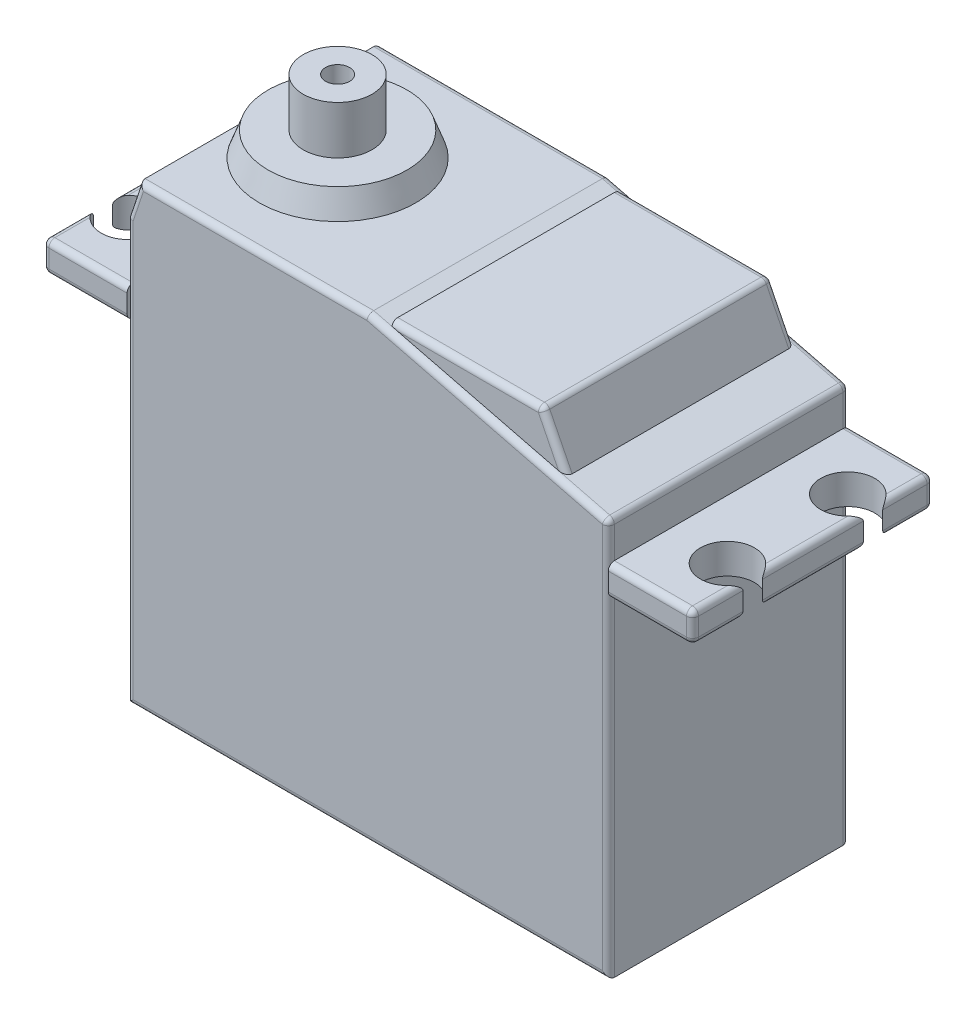
SolidWorks part; units mm, degrees
material "ABS"
ref_plane "Front Plane" through (0, 0, 0) normal (0, 0, 1) x (1, 0, 0)
ref_plane "Top Plane" through (0, 0, 0) normal (0, 1, 0) x (1, 0, 0)
ref_plane "Right Plane" through (0, 0, 0) normal (1, 0, 0) x (0, 0, -1)
sketch "Sketch2" plane through (0, 0, 0) normal (0, 1, 0) x (1, 0, 0)
  line L1 (0, 0) -> (40, 0)
  line L2 (0, 0) -> (0, 20)
  line L3 (0, 20) -> (40, 20)
  line L4 (40, 0) -> (40, 20)
  dimension "D1" = 40
  dimension "D2" = 20
extrude "Boss-Extrude1" add sketch "Sketch2" along normal blind 38
sketch "Sketch3" plane through (0, 38, 0) normal (0, 1, 0) x (1, 0, 0)
  line L0 (0, 20) -> (0, 0) construction
  line L1 (40, 20) -> (0, 20) construction
  circle A0 centre (7.5, 10) radius 6.5
  dimension "D1" = 13
  dimension "D2" = 7.5
  dimension "D3" = 10
extrude "Boss-Extrude2" add sketch "Sketch3" along normal blind 2 draft 20
sketch "Sketch4" plane through (0, 40, 0) normal (0, 1, 0) x (1, 0, 0)
  circle A0 centre (7.5, 10) radius 2.8575
  dimension "D1" = 5.715
extrude "Boss-Extrude3" add sketch "Sketch4" along normal blind 4
sketch "Sketch5" plane through (0, 44, 0) normal (0, 1, 0) x (1, 0, 0)
  circle A0 centre (7.5, 10) radius 1
  dimension "D1" = 2
extrude "Cut-Extrude1" cut sketch "Sketch5" against normal blind 5
sketch "Sketch6" plane through (0, 38, 0) normal (0, 1, 0) x (1, 0, 0)
  line L0 (40, 0) -> (47, 0)
  line L1 (47, 0) -> (47, 4.1922)
  line L2 (47, 20) -> (40, 20)
  line L3 (40, 20) -> (40, 0)
  line L4 (47.14, 10) -> (40, 10) construction
  line L5 (20, 20) -> (20, 0) construction
  line L6 (40, 20) -> (0, 20) construction
  line L7 (0, 0) -> (40, 0) construction
  line L8 (-7.14, 10) -> (0, 10) construction
  line L9 (-7, 15.8078) -> (-7, 20)
  line L10 (-7, 5.8078) -> (-7, 14.1922)
  line L11 (0, 20) -> (0, 0)
  line L12 (-7, 20) -> (0, 20)
  line L13 (47, 5.8078) -> (47, 14.1922)
  line L14 (47, 15.8078) -> (47, 20)
  line L15 (-7, 0) -> (-7, 4.1922)
  line L16 (0, 0) -> (-7, 0)
  arc A0 (47, 5.8078) -> (47, 4.1922) centre (44.9, 5) ccw
  arc A1 (47, 15.8078) -> (47, 14.1922) centre (44.9, 15) ccw
  arc A2 (-7, 15.8078) -> (-7, 14.1922) centre (-4.9, 15) cw
  arc A3 (-7, 5.8078) -> (-7, 4.1922) centre (-4.9, 5) cw
  dimension "D2" = 4.5
  dimension "D3" = 10
  dimension "D5" = 2.1
  dimension "D6" = 4.1922
  dimension "D1" = 7
  dimension "D4" = 5
extrude "Boss-Extrude6" add sketch "Sketch6" against normal blind 2.5 from offset 8 separate body offset against normal yes
sketch "Sketch8" plane through (0, 0, 0) normal (0, 0, 1) x (1, 0, 0)
  line L0 (20, 38) -> (40, 33)
  line L1 (0, 38) -> (40, 38) construction
  line L2 (40, 38) -> (40, 0) construction
  line L3 (20, 38) -> (40, 38)
  line L4 (40, 38) -> (40, 33)
  line L5 (0, 38) -> (0, 35)
  line L6 (0, 38) -> (0, 0) construction
  line L7 (0, 35) -> (1, 38)
  line L8 (1, 38) -> (0, 38)
  dimension "D1" = 5
  dimension "D2" = 3
  dimension "D3" = 1
extrude "Cut-Extrude5" cut sketch "Sketch8" against normal through all
sketch "Sketch9" plane through (0, 0, 0) normal (0, 0, 1) x (1, 0, 0)
  line L0 (21.5, 38) -> (34, 38)
  line L1 (34, 38) -> (36, 34)
  line L2 (20, 38) -> (40, 33) construction
  line L3 (21.5, 37.625) -> (36, 34)
  line L4 (21.5, 37.625) -> (21.5, 38)
  dimension "D1" = 12.5
  dimension "D2" = 4
  dimension "D3" = 1.5
extrude "Boss-Extrude7" add sketch "Sketch9" against normal blind 19 from offset 0.5 offset against normal yes
fillet "Fillet1" radius 0.5 18 edges at (30, 35.5, 0) (40, 16.5, 0) (20, 0, 0) (0, 17.5, 0) (0.5, 36.5, 0) (10.5, 38, 0) (34, 38, -10) (40, 33, -10) (27.75, 38, -19.5) (35, 36, -19.5) (35, 36, -0.5) (27.75, 38, -0.5) (0.5, 36.5, -20) (20, 0, -20) (30, 35.5, -20) (10.5, 38, -20) (0, 17.5, -20) (40, 16.5, -20)
fillet "Fillet3" radius 0.5 12 edges at (-7, 28.75, 0) (-7, 28.75, -20) (-3.5, 27.5, -20) (-3.5, 30, -20) (-3.5, 30, 0) (-3.5, 27.5, 0) (-7, 27.5, -2.0961) (-7, 27.5, -10) (-7, 27.5, -17.9039) (-7, 30, -17.9039) (-7, 30, -10) (-7, 30, -2.0961)
fillet "Fillet4" radius 0.5 12 edges at (43.5, 27.5, -20) (43.5, 30, -20) (43.5, 27.5, 0) (43.5, 30, 0) (47, 30, -17.9039) (47, 27.5, -17.9039) (47, 27.5, -10) (47, 27.5, -2.0961) (47, 30, -2.0961) (47, 30, -10) (47, 28.75, -20) (47, 28.75, 0)
